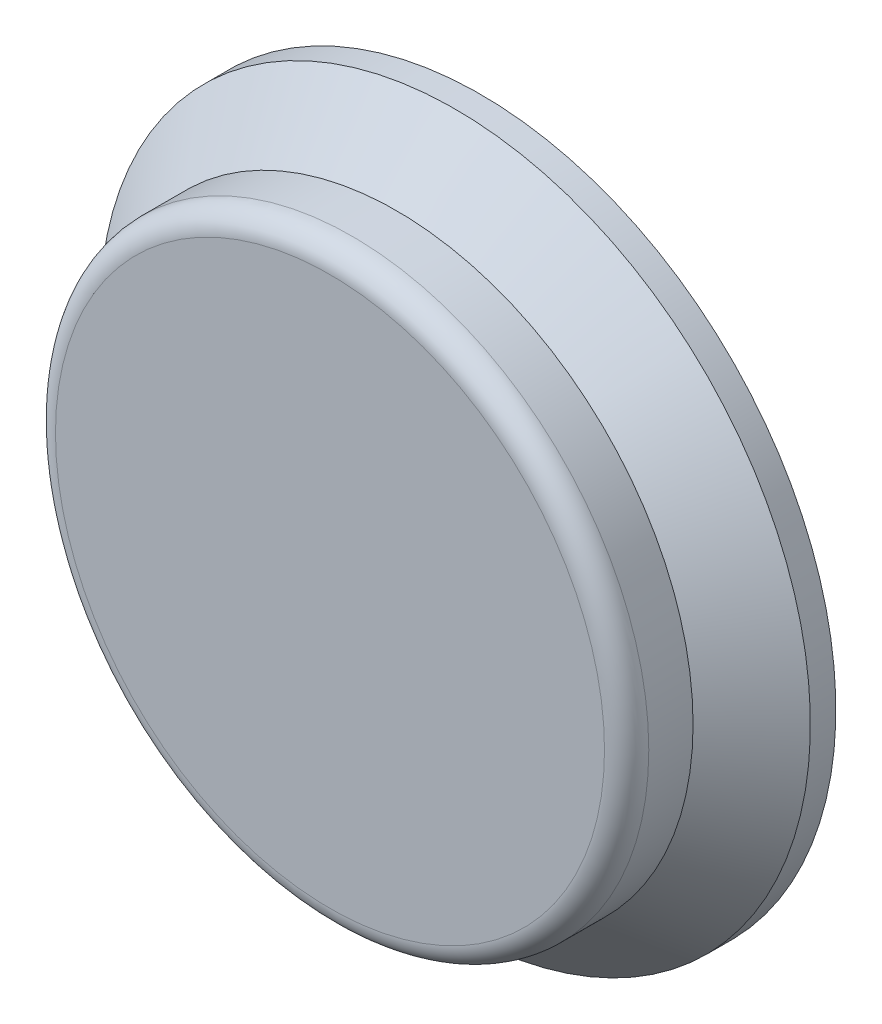
SolidWorks part; units mm, degrees
ref_plane "Piano frontale" through (0, 0, 0) normal (0, 0, 1) x (1, 0, 0)
ref_plane "Piano superiore" through (0, 0, 0) normal (0, 1, 0) x (1, 0, 0)
ref_plane "Piano destro" through (0, 0, 0) normal (1, 0, 0) x (0, 0, -1)
sketch "Schizzo1" plane through (0, 0, 0) normal (0, 0, 1) x (1, 0, 0)
  circle A0 centre (0, 0) radius 16.05
  dimension "D1" = 32.1
extrude "Estrusione-Estrusione1" add sketch "Schizzo1" along normal blind 3.8
sketch "Schizzo2" plane through (0, 0, 3.8) normal (0, 0, 1) x (1, 0, 0)
  circle A0 centre (0, 0) radius 13.4
  dimension "D1" = 26.8
extrude "Estrusione-Estrusione2" add sketch "Schizzo2" along normal blind 3
chamfer "Smusso1" distance 2.65 angle 45 1 edges at (16.05, 0, 3.8)
fillet "Raccordo1" radius 1 1 edges at (13.4, 0, 6.8)
sketch "Schizzo3" plane through (0, 0, 0) normal (0, 0, -1) x (-1, 0, 0)
  circle A0 centre (0, 0) radius 13.25
  dimension "D1" = 26.5
extrude "Taglio-Estrusione1" cut sketch "Schizzo3" against normal blind 5
chamfer "Smusso2" distance 1.5 angle 45 1 edges at (-13.25, 0, 0)
